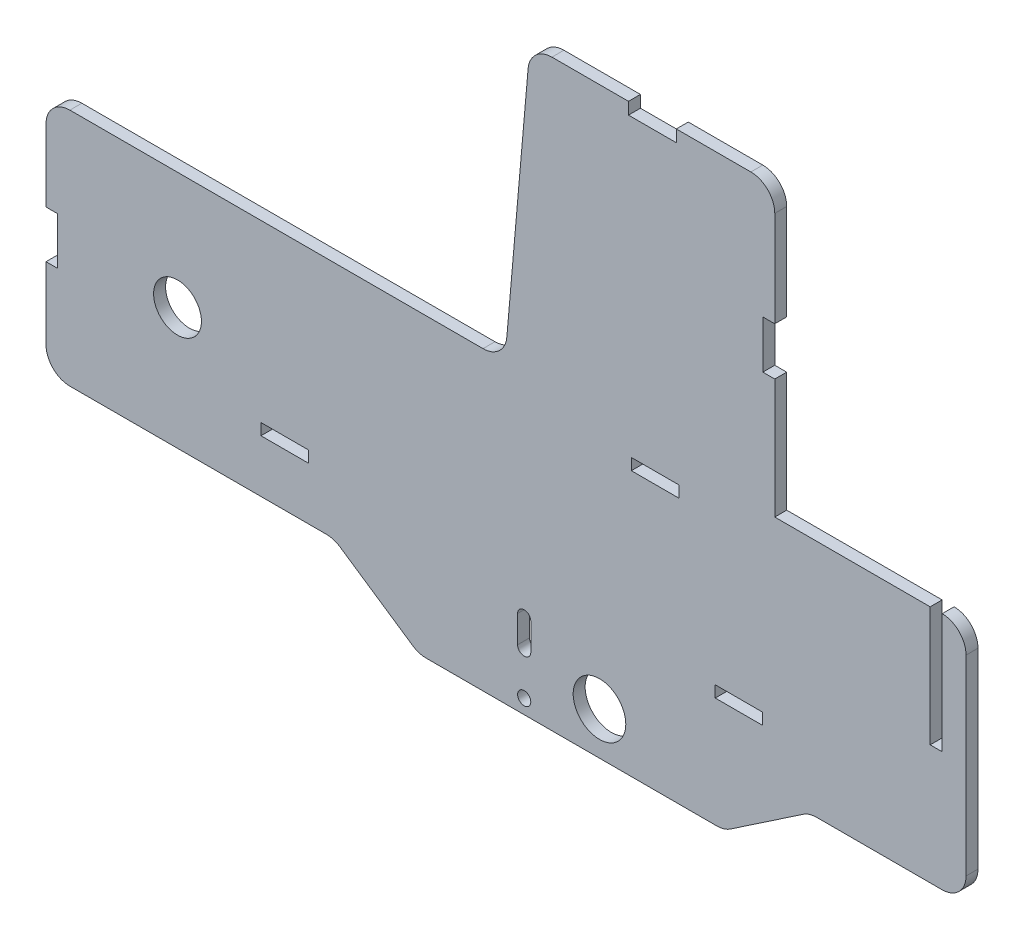
SolidWorks part; units mm, degrees
ref_plane "Front Plane" through (0, 0, 0) normal (0, 0, 1) x (1, 0, 0)
ref_plane "Top Plane" through (0, 0, 0) normal (0, 1, 0) x (1, 0, 0)
ref_plane "Right Plane" through (0, 0, 0) normal (1, 0, 0) x (0, 0, -1)
sketch "Sketch1" plane through (0, 0, 0) normal (0, 0, 1) x (1, 0, 0)
  line L0 (62.1239, 7.4217) -> (131.9663, 7.4217)
  line L1 (201.8088, 13.7717) -> (201.8088, 77.2717)
  line L2 (201.8088, 77.2717) -> (151.0088, 77.2717)
  line L3 (151.0088, 77.2717) -> (151.0088, 153.4717)
  line L4 (151.0088, 153.4717) -> (86.0089, 153.4717)
  line L5 (86.0089, 153.4717) -> (79.3423, 77.2717)
  line L6 (79.3423, 77.2717) -> (-42.5392, 77.2717)
  line L7 (-42.5392, 77.2717) -> (-42.5392, 13.7717)
  line L9 (-42.5392, 13.7717) -> (46.6174, 13.7717)
  line L10 (46.6174, 13.7717) -> (62.1239, 7.4217)
  line L11 (201.8088, 13.7717) -> (147.4729, 13.7717)
  line L12 (147.4729, 13.7717) -> (131.9663, 7.4217)
  point P1 (0, 0)
  point P2 (41.4965, 77.7665)
  point P12 (30.6476, 128.0717)
  dimension "D1" = 244.348
  dimension "D2" = 6.35
  dimension "D3" = 76.2
  dimension "D4" = 63.5
  dimension "D5" = 50.8
  dimension "D6" = 16.7564
  dimension "D7" = 16.7564
  dimension "D8" = 63.5
  dimension "D9" = 95
  dimension "D10" = 71.6665
extrude "Main Side" add sketch "Sketch1" along normal blind 3.175
sketch "Sketch2" plane through (0, 0, 3.175) normal (0, 0, 1) x (1, 0, 0)
  line L0 (-39.4912, 77.2717) -> (-39.4912, 13.7717) construction
  line L15 (79.3423, 77.2717) -> (-42.5392, 77.2717) construction
  line L16 (-42.5392, 77.2717) -> (-42.5392, 13.7717) construction
  line L26 (-39.4912, 18.5744) -> (201.8088, 18.5744) construction
  line L27 (201.8088, 13.7717) -> (201.8088, 77.2717) construction
  line L28 (81.1588, 18.5744) -> (81.1588, 153.4717) construction
  line L29 (151.0088, 153.4717) -> (86.0089, 153.4717) construction
  line L30 (81.1588, 36.7006) -> (201.8088, 36.7006) construction
  line L41 (62.1239, 7.4217) -> (131.9663, 7.4217) construction
  line L42 (135.1973, 30.7897) -> (147.7703, 30.7897)
  line L43 (135.1973, 30.7897) -> (135.1973, 27.7417)
  line L44 (135.1973, 27.7417) -> (147.7703, 27.7417)
  line L45 (147.7703, 30.7897) -> (147.7703, 27.7417)
  line L46 (14.5473, 30.7897) -> (14.5473, 27.7417)
  line L47 (27.1203, 27.7417) -> (14.5473, 27.7417)
  line L48 (27.1203, 30.7897) -> (27.1203, 27.7417)
  line L49 (27.1203, 30.7897) -> (14.5473, 30.7897)
  line L51 (-42.5392, 13.7717) -> (46.6174, 13.7717) construction
  point P20 (141.4838, 30.7897)
  point P21 (141.4838, 36.7006)
  dimension "D1" = 12.573
  dimension "D2" = 3.048
  dimension "D3" = 20.32
  dimension "D4" = 3.048
extrude "Bottom Plate Holes" cut sketch "Sketch2" against normal through all
sketch "Sketch3" plane through (0, 0, 3.175) normal (0, 0, 1) x (1, 0, 0)
  line L1 (112.9088, 71.9377) -> (125.6088, 71.9377)
  line L2 (112.9088, 71.9377) -> (112.9088, 68.8897)
  line L3 (112.9088, 68.8897) -> (125.6088, 68.8897)
  line L4 (125.6088, 71.9377) -> (125.6088, 68.8897)
  line L5 (201.8088, 13.7717) -> (201.8088, 77.2717) construction
  line L6 (147.7703, 30.7897) -> (135.1973, 30.7897) construction
  dimension "D1" = 12.7
  dimension "D2" = 3.048
  dimension "D3" = 38.1
  dimension "D4" = 76.2
extrude "Cut-Extrude1" cut sketch "Sketch3" against normal through all
sketch "Sketch4" plane through (0, 0, 3.175) normal (0, 0, 1) x (1, 0, 0)
  line L0 (-42.5392, 77.2717) -> (-42.5392, 13.7717) construction
  line L1 (-42.5392, 51.8082) -> (-39.4912, 51.8082)
  line L2 (-42.5392, 51.8082) -> (-42.5392, 39.2352)
  line L3 (-42.5392, 39.2352) -> (-39.4912, 39.2352)
  line L4 (-39.4912, 51.8082) -> (-39.4912, 39.2352)
  point P6 (-42.5392, 45.5217)
  point P7 (-42.5392, 45.5217)
  dimension "D1" = 3.048
  dimension "D2" = 12.573
extrude "Cut-Extrude2" cut sketch "Sketch4" against normal through all
sketch "Sketch5" plane through (0, 0, 3.175) normal (0, 0, 1) x (1, 0, 0)
  line L0 (201.8088, 77.2717) -> (151.0088, 77.2717) construction
  line L1 (192.2838, 77.2717) -> (195.4588, 77.2717)
  line L2 (192.2838, 77.2717) -> (192.2838, 45.5217)
  line L3 (192.2838, 45.5217) -> (195.4588, 45.5217)
  line L4 (195.4588, 77.2717) -> (195.4588, 45.5217)
  line L5 (201.8088, 13.7717) -> (201.8088, 77.2717) construction
  dimension "D1" = 3.175
  dimension "D2" = 31.75
  dimension "D3" = 6.35
extrude "Cut-Extrude3" cut sketch "Sketch5" against normal through all
sketch "Sketch6" plane through (0, 0, 3.175) normal (0, 0, 1) x (1, 0, 0)
  line L0 (-42.5392, 77.2717) -> (-42.5392, 51.8082) construction
  line L1 (79.3423, 77.2717) -> (-42.5392, 77.2717) construction
  circle A0 centre (-7.6142, 46.1567) radius 6.35
  dimension "D2" = 31.115
  dimension "D3" = 12.7
  dimension "D1" = 34.925
extrude "Cut-Extrude4" cut sketch "Sketch6" against normal through all
sketch "Sketch7" plane through (0, 0, 3.175) normal (0, 0, 1) x (1, 0, 0)
  line L0 (151.0088, 153.4717) -> (86.0089, 153.4717) construction
  line L1 (112.1588, 153.4717) -> (124.8588, 153.4717)
  line L2 (112.1588, 153.4717) -> (112.1588, 150.2967)
  line L3 (112.1588, 150.2967) -> (124.8588, 150.2967)
  line L4 (124.8588, 153.4717) -> (124.8588, 150.2967)
  point P6 (118.5088, 153.4717)
  point P7 (118.5088, 153.4717)
  dimension "D1" = 3.175
  dimension "D2" = 12.7
extrude "Cut-Extrude5" cut sketch "Sketch7" against normal through all
sketch "Sketch8" plane through (0, 0, 3.175) normal (0, 0, 1) x (1, 0, 0)
  line L0 (151.0088, 77.2717) -> (151.0088, 153.4717) construction
  line L1 (147.8338, 121.7217) -> (151.0088, 121.7217)
  line L2 (147.8338, 121.7217) -> (147.8338, 109.0217)
  line L3 (147.8338, 109.0217) -> (151.0088, 109.0217)
  line L4 (151.0088, 121.7217) -> (151.0088, 109.0217)
  point P6 (151.0088, 115.3717)
  point P7 (151.0088, 115.3717)
  dimension "D1" = 3.175
  dimension "D2" = 12.7
extrude "Cut-Extrude6" cut sketch "Sketch8" against normal through all
sketch "Sketch13" plane through (0, 0, 3.175) normal (0, 0, 1) x (1, 0, 0)
  line L1 (-42.5392, 13.7717) -> (46.6174, 13.7717) construction
  line L4 (147.4729, 13.7717) -> (201.8088, 13.7717) construction
  line L5 (33.9174, 13.7717) -> (56.4826, -1.4683)
  line L6 (56.4826, -1.4683) -> (137.6077, -1.4683)
  line L7 (137.6077, -1.4683) -> (160.1729, 13.7717)
  line L8 (33.9174, 13.7717) -> (46.6174, 13.7717)
  line L9 (46.6174, 13.7717) -> (62.1239, 7.4217)
  line L10 (62.1239, 7.4217) -> (131.9663, 7.4217)
  line L11 (131.9663, 7.4217) -> (147.4729, 13.7717)
  line L12 (147.4729, 13.7717) -> (160.1729, 13.7717)
  dimension "D1" = 8.89
  dimension "D2" = 12.7
  dimension "D3" = 12.7
  dimension "D4" = 145.966
  dimension "D5" = 145.966
extrude "Boss-Extrude2" add sketch "Sketch13" against normal blind 3.175
sketch "Sketch10" plane through (0, 0, 3.175) normal (0, 0, 1) x (1, 0, 0)
  line L0 (84.4608, 20.934) -> (84.4608, 13.7493) construction
  line L1 (86.2108, 20.934) -> (86.2108, 13.7493)
  line L2 (82.7108, 20.934) -> (82.7108, 13.7493)
  line L3 (84.4608, 17.3417) -> (84.4608, 2.3417) construction
  line L4 (-42.5392, 39.2352) -> (-42.5392, 13.7717) construction
  line L6 (56.4826, -1.4683) -> (137.6077, -1.4683) construction
  circle A0 centre (84.4608, 2.3417) radius 1.75
  arc A1 (86.2108, 20.934) -> (82.7108, 20.934) centre (84.4608, 20.934) ccw
  arc A2 (82.7108, 13.7493) -> (86.2108, 13.7493) centre (84.4608, 13.7493) ccw
  circle A3 centre (104.4608, 9.8417) radius 6.985
  point P4 (84.4608, 17.3417)
  point P13 (84.4608, 9.8417)
  dimension "D2" = 3.5
  dimension "D4" = 13.97
  dimension "D6" = 7.1848
  dimension "D1" = 15
  dimension "D3" = 3.5
  dimension "D5" = 20
  dimension "D7" = 127
  dimension "D8" = 3.81
extrude "Cut-Extrude7" cut sketch "Sketch10" against normal through all
fillet "Fillet1" radius 6.35 11 edges at (151.0088, 153.4717, 1.5875) (86.0089, 153.4717, 1.5875) (79.3423, 77.2717, 1.5875) (201.8088, 13.7717, 1.5875) (-42.5392, 13.7717, 1.5875) (201.8088, 77.2717, 1.5875) (-42.5392, 77.2717, 1.5875) (160.1729, 13.7717, 1.5875) (137.6077, -1.4683, 1.5875) (56.4826, -1.4683, 1.5875) (33.9174, 13.7717, 1.5875)
